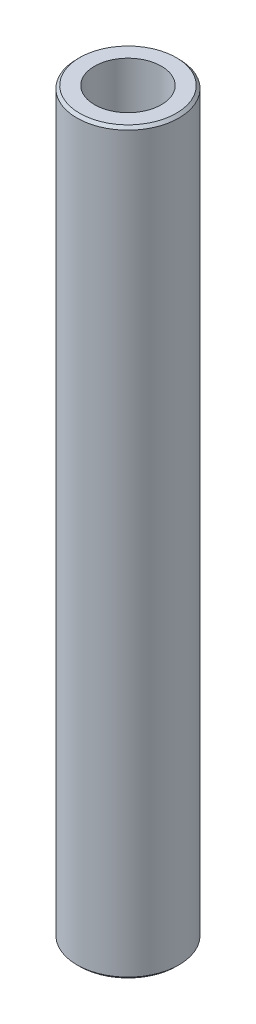
SolidWorks part; units mm, degrees
ref_plane "Front Plane" through (0, 0, 0) normal (0, 0, 1) x (1, 0, 0)
ref_plane "Top Plane" through (0, 0, 0) normal (0, 1, 0) x (1, 0, 0)
ref_plane "Right Plane" through (0, 0, 0) normal (1, 0, 0) x (0, 0, -1)
sketch "Sketch1" plane through (0, 0, 0) normal (0, 1, 0) x (1, 0, 0)
  circle A0 centre (0, 0) radius 15
  dimension "SHAFT_OD" = 30
extrude "Boss-Extrude1" add sketch "Sketch1" along normal blind 217.3222
sketch "Sketch2" plane through (0, 0, 0) normal (0, 1, 0) x (1, 0, 0)
  circle A0 centre (0, 0) radius 9.8297
  dimension "BORE_D" = 19.6594
extrude "Cut-Extrude1" cut sketch "Sketch2" along normal through all
chamfer "Chamfer1" distance 0.8023 angle 44.706 2 edges at (0, 217.3222, 15) (0, 0, 15) first distance on face at (0, 217.3222, 15) first distance on face at (0, 0, 9.8297)
